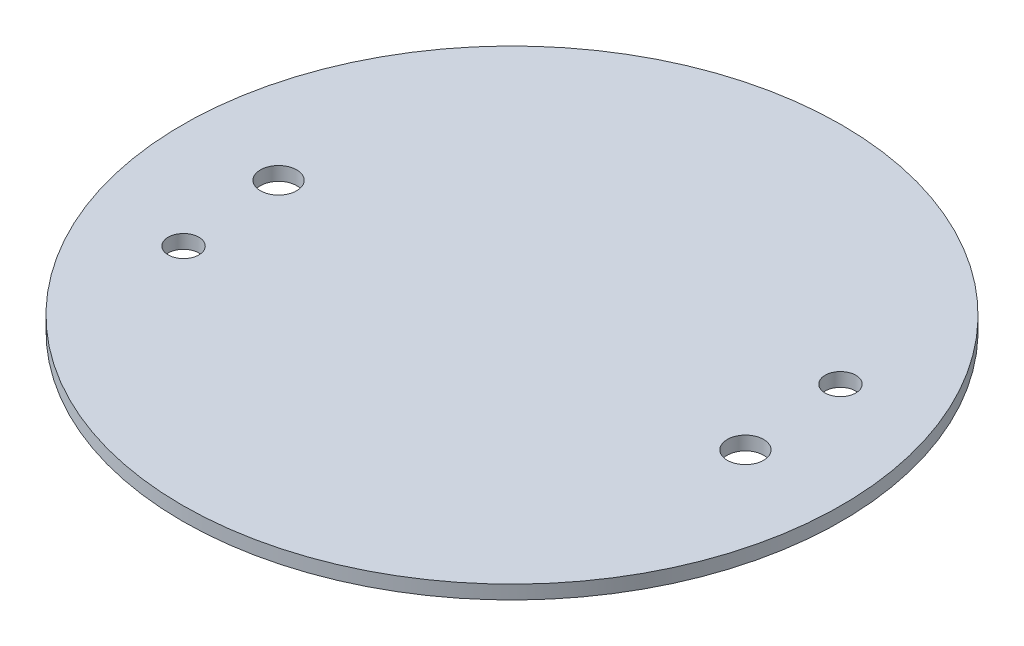
SolidWorks part; units mm, degrees
ref_plane "Front Plane" through (0, 0, 0) normal (0, 0, 1) x (1, 0, 0)
ref_plane "Top Plane" through (0, 0, 0) normal (0, 1, 0) x (1, 0, 0)
ref_plane "Right Plane" through (0, 0, 0) normal (1, 0, 0) x (0, 0, -1)
sketch "Sketch1" plane through (0, 0, 0) normal (0, 1, 0) x (1, 0, 0)
  circle A0 centre (0, 0) radius 76.2
extrude "Boss-Extrude1" add sketch "Sketch1" along normal blind 3.175
sketch "Sketch2" plane through (0, 3.175, 0) normal (0, 1, 0) x (1, 0, 0)
  line L0 (53.975, 0) -> (-53.975, 0) construction
  line L1 (-51.7955, -24.1526) -> (51.7955, 24.1526) construction
  circle A2 centre (-51.7955, -24.1526) radius 3.556
  circle A3 centre (51.7955, 24.1526) radius 3.556
  circle A4 centre (-53.975, 0) radius 4.191
  circle A5 centre (53.975, 0) radius 4.191
  point P3 (0, 0)
  point P5 (0, 0)
  point P11 (0, 0)
extrude "Cut-Extrude1" cut sketch "Sketch2" against normal blind 3.175
